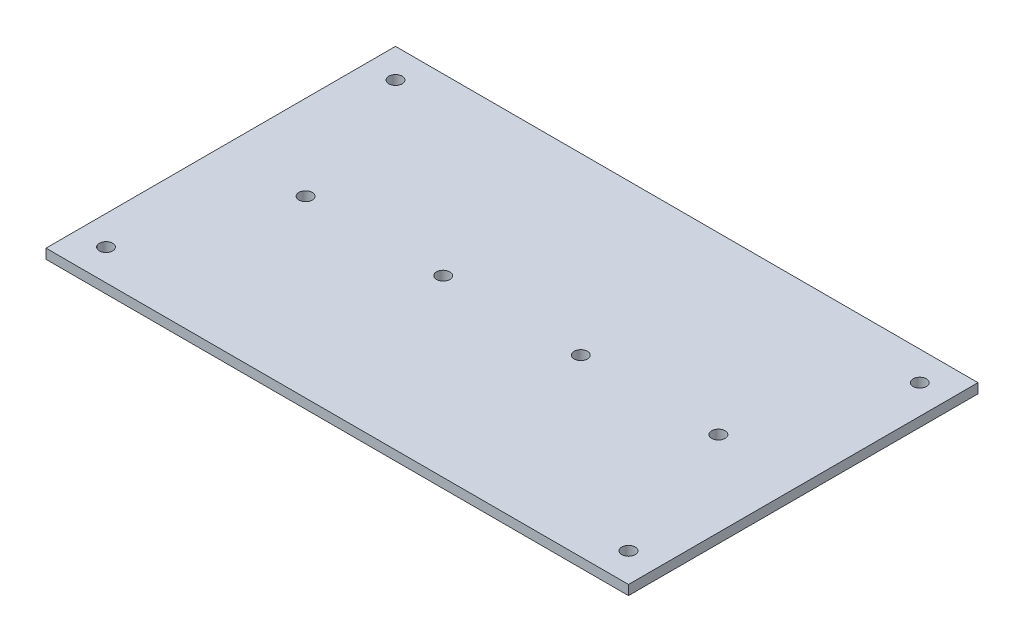
SolidWorks part; units mm, degrees
ref_plane "Front Plane" through (0, 0, 0) normal (0, 0, 1) x (1, 0, 0)
ref_plane "Top Plane" through (0, 0, 0) normal (0, 1, 0) x (1, 0, 0)
ref_plane "Right Plane" through (0, 0, 0) normal (1, 0, 0) x (0, 0, -1)
sketch "Sketch1" plane through (0, 0, 0) normal (0, 1, 0) x (1, 0, 0)
  line L1 (0, 0) -> (381, 0)
  line L2 (0, 0) -> (0, -228.6)
  line L3 (0, -228.6) -> (381, -228.6)
  line L4 (381, 0) -> (381, -228.6)
  dimension "D1" = 381
  dimension "D2" = 228.6
extrude "Base" add sketch "Sketch1" against normal blind 6.35
sketch "Sketch9" plane through (0, 0, 0) normal (0, 1, 0) x (1, 0, 0)
  line L0 (0, -114.3) -> (381, -114.3) construction
  line L1 (0, 0) -> (0, -228.6) construction
  line L2 (381, -228.6) -> (381, 0) construction
  line L3 (55.5, -114.3) -> (145.4998, -114.3) construction
  point P7 (54, -99.3)
  point P21 (304, -129.3)
  point P22 (304, -99.3)
  point P23 (204, -129.3)
  point P24 (204, -99.3)
  point P25 (104, -129.3)
  point P26 (104, -99.3)
  point P27 (154, -99.3)
  point P28 (54, -129.3)
  point P29 (154, -129.3)
  point P30 (55.5, -114.3)
  point P31 (145.4998, -114.3)
  point P33 (235.4996, -114.3)
  point P34 (325.4995, -114.3)
  dimension "D2" = 89.9998
  dimension "D3" = 4
  dimension "D1" = 55.5
hole_wizard "Hole for 1/4 Blind Fasteners (B,BS)1" positions "Sketch10" profile "Sketch11" hole size "1/4-20" standard "PEM® Inch" end condition through all
sketch "Sketch10" plane through (0, 0, 0) normal (0, 1, 0) x (1, 0, 0)
  point P42 (55.5, -114.3)
  point P45 (145.4998, -114.3)
  point P48 (235.4996, -114.3)
  point P51 (325.4995, -114.3)
sketch "Sketch11" plane through (55.5, 0, 114.3) normal (1, 0, 0) x (0, 0, 1)
  line L0 (0, 0) -> (0, 6.35)
  line L1 (0, 6.35) -> (4.3688, 6.35)
  line L2 (4.3688, 6.35) -> (4.3688, 0)
  line L5 (4.3688, 0) -> (0, 0)
  line L11 (0, -6.35) -> (0, 107.95) construction
  dimension "Thru Hole Dia." = 8.7376
  dimension "Thru Hole Depth" = 6.35
sketch "Sketch12" plane through (0, -6.35, 0) normal (0, -1, 0) x (1, 0, 0)
  line L0 (0, 228.6) -> (381, 228.6) construction
  line L1 (8, 220.6) -> (38, 220.6)
  line L2 (8, 220.6) -> (8, 190.6)
  line L3 (8, 190.6) -> (38, 190.6)
  line L4 (38, 220.6) -> (38, 190.6)
  line L5 (0, 0) -> (0, 228.6) construction
  line L6 (190.5, 228.6) -> (190.5, 0) construction
  line L7 (381, 0) -> (0, 0) construction
  line L8 (0, 114.3) -> (381, 114.3) construction
  line L9 (381, 228.6) -> (381, 0) construction
  line L10 (8, 38) -> (38, 38)
  line L11 (38, 8) -> (38, 38)
  line L12 (8, 8) -> (38, 8)
  line L13 (8, 8) -> (8, 38)
  line L14 (373, 8) -> (373, 38)
  line L15 (373, 8) -> (343, 8)
  line L16 (343, 8) -> (343, 38)
  line L17 (373, 38) -> (343, 38)
  line L18 (373, 190.6) -> (343, 190.6)
  line L19 (343, 220.6) -> (343, 190.6)
  line L20 (373, 220.6) -> (343, 220.6)
  line L21 (373, 220.6) -> (373, 190.6)
  dimension "D1" = 30
  dimension "D2" = 30
extrude "Boss-Extrude1" [suppressed] add sketch "Sketch12" along normal blind 10
sketch "Sketch13" plane through (0, 0, 0) normal (0, 1, 0) x (1, 0, 0)
  line L1 (0, 0) -> (0, -228.6) construction
  line L2 (381, 0) -> (0, 0) construction
  line L3 (381, -228.6) -> (381, 0) construction
  line L4 (0, -228.6) -> (381, -228.6) construction
  point P0 (19.05, -19.05)
  point P1 (361.95, -19.05)
  point P2 (361.95, -209.55)
  point P3 (19.05, -209.55)
  dimension "D1" = 19.05
  dimension "D2" = 19.05
  dimension "D3" = 19.05
  dimension "D4" = 19.05
  dimension "D5" = 19.05
  dimension "D6" = 19.05
  dimension "D7" = 19.05
  dimension "D8" = 19.05
hole_wizard "Hole for 1/4 Blind Fasteners (B,BS)2" positions "Sketch14" profile "Sketch15" hole size "1/4-20" standard "PEM® Inch" end condition through all
sketch "Sketch14" plane through (0, 0, 0) normal (0, 1, 0) x (1, 0, 0)
  point P0 (19.05, -19.05)
  point P3 (19.0341, -208.3655)
  point P7 (361.95, -19.05)
  point P18 (361.95, -209.55)
sketch "Sketch15" plane through (19.05, 0, 19.05) normal (1, 0, 0) x (0, 0, 1)
  line L0 (0, 0) -> (0, 6.35)
  line L1 (0, 6.35) -> (4.3688, 6.35)
  line L2 (4.3688, 6.35) -> (4.3688, 0)
  line L5 (4.3688, 0) -> (0, 0)
  line L11 (0, -6.35) -> (0, 107.95) construction
  dimension "Thru Hole Dia." = 8.7376
  dimension "Thru Hole Depth" = 6.35
